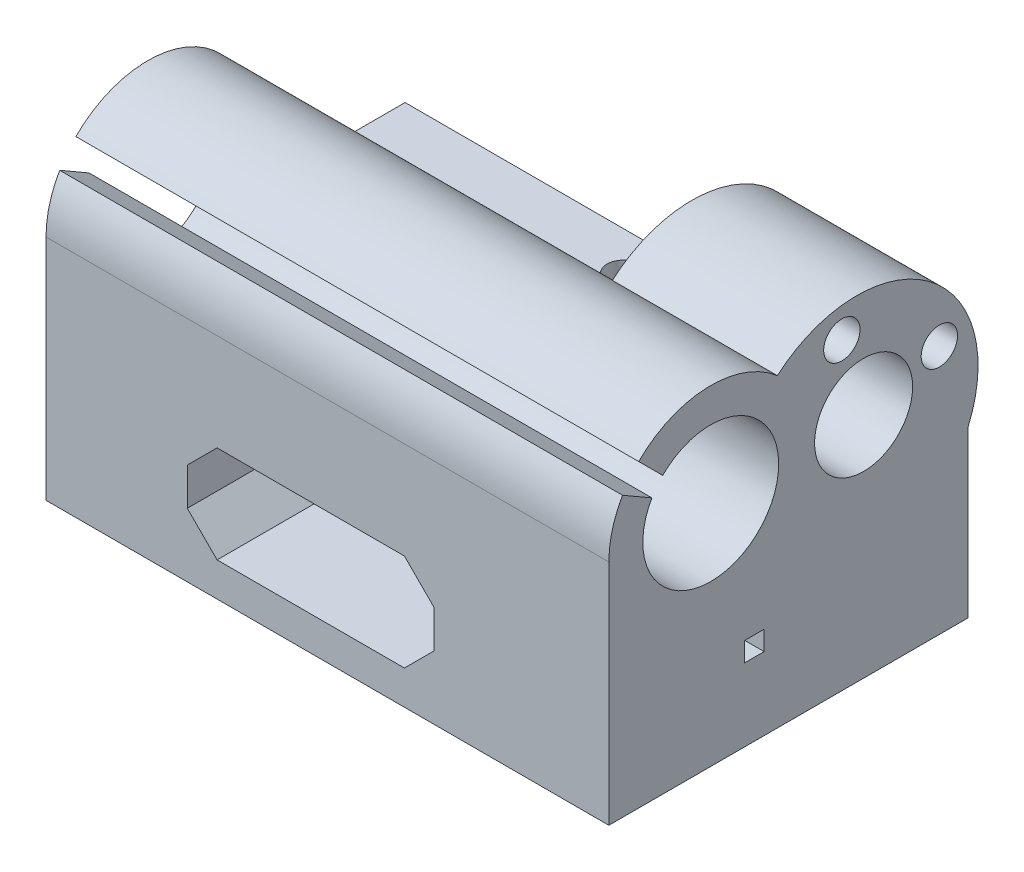
SolidWorks part; units mm, degrees
ref_plane "Front Plane" through (0, 0, 0) normal (0, 0, 1) x (1, 0, 0)
ref_plane "Top Plane" through (0, 0, 0) normal (0, 1, 0) x (1, 0, 0)
ref_plane "Right Plane" through (0, 0, 0) normal (1, 0, 0) x (0, 0, -1)
sketch "Sketch2" plane through (0, 0, 0) normal (0, 1, 0) x (1, 0, 0)
  line L1 (-29, -18.5) -> (29, -18.5)
  line L2 (-29, -18.5) -> (-29, 18.5)
  line L3 (-29, 18.5) -> (29, 18.5)
  line L4 (29, -18.5) -> (29, 18.5)
  line L5 (-29, -18.5) -> (29, 18.5) construction
  line L6 (-29, 18.5) -> (29, -18.5) construction
  point P0 (0, 0)
  dimension "D1" = 58
  dimension "D2" = 37
extrude "Boss-Extrude1" add sketch "Sketch2" along normal blind 17
sketch "Sketch3" plane through (29, 0, 0) normal (1, 0, 0) x (0, 0, -1)
  line L0 (-18.5, 0) -> (18.5, 0) construction
  line L1 (-18.5, 23.5) -> (-18.5, 17)
  line L2 (-18.5, 17) -> (-18.5, 0) construction
  line L5 (2.5, 23.5) -> (2.5, 17)
  line L6 (-18.5, 17) -> (18.5, 17) construction
  line L7 (-18.5, 17) -> (2.5, 17)
  arc A0 (2.5, 23.5) -> (-18.5, 23.5) centre (-8, 23.5) ccw
  dimension "D2" = 21
  dimension "D4" = 23.5
  dimension "D5" = 10.5
extrude "Boss-Extrude2" add sketch "Sketch3" against normal up to surface (58 mm away) up to face at (-29, 8.5, 0)
sketch "Sketch4" plane through (29, 0, 0) normal (1, 0, 0) x (0, 0, -1)
  line L1 (-18.5, 0) -> (18.5, 0) construction
  circle A0 centre (7.0436, 22) radius 12.5
  dimension "D1" = 25
  dimension "D2" = 22
extrude "Boss-Extrude3" add sketch "Sketch4" against normal blind 17
sketch "Sketch5" plane through (0, 0, -18.5) normal (0, 0, -1) x (-1, 0, 0)
  line L0 (-11, 6.57) -> (-11, 10.427)
  line L1 (-11, 10.427) -> (-7.93, 13.497)
  line L2 (-7.93, 13.497) -> (11.37, 13.497)
  line L3 (11.37, 13.497) -> (14.44, 10.427)
  line L4 (14.44, 10.427) -> (14.44, 6.57)
  line L5 (14.44, 6.57) -> (11.37, 3.5)
  line L6 (11.37, 3.5) -> (-7.93, 3.5)
  line L7 (-7.93, 3.5) -> (-11, 6.57)
  line L8 (-29, 0) -> (29, 0) construction
  line L9 (-29, 17) -> (-29, 0) construction
  dimension "D1" = 3.857
  dimension "D2" = 3.857
  dimension "D3" = 135
  dimension "D4" = 135
  dimension "D5" = 3.07
  dimension "D6" = 3.07
  dimension "D7" = 3.07
  dimension "D8" = 3.07
  dimension "D9" = 19.3
  dimension "D10" = 3.5
  dimension "D11" = 18
extrude "Cut-Extrude1" cut sketch "Sketch5" against normal through all
sketch "Sketch6" plane through (0, 0, -18.5) normal (0, 0, -1) x (-1, 0, 0)
  line L0 (-29, 0) -> (29, 0) construction
  line L1 (-29, 17) -> (-29, 0) construction
  circle A0 centre (-23, 8.5) radius 4.076
  circle A1 centre (22, 8.5) radius 4.076
  dimension "D5" = 8.152
  dimension "D6" = 8.152
  dimension "D1" = 8.5
  dimension "D2" = 8.5
  dimension "D3" = 6
  dimension "D4" = 51
extrude "Cut-Extrude2" cut sketch "Sketch6" against normal blind 23
sketch "Sketch7" plane through (29, 0, 0) normal (1, 0, 0) x (0, 0, -1)
  line L0 (-18.5, 23.5) -> (-18.5, 0) construction
  line L1 (-18.5, 0) -> (18.5, 0) construction
  circle A0 centre (-8, 23.5) radius 7
  circle A1 centre (7.7501, 23.5) radius 5.05
  dimension "D1" = 10.1
  dimension "D2" = 14
  dimension "D3" = 26.2501
  dimension "D4" = 23.5
extrude "Cut-Extrude3" cut sketch "Sketch7" against normal through all
sketch "Sketch8" plane through (29, 0, 0) normal (1, 0, 0) x (0, 0, -1)
  line L0 (7.7501, 23.5) -> (5.5097, 31.31) construction
  line L3 (7.7501, 23.5) -> (15.5601, 25.7405) construction
  line L4 (5.5097, 31.31) -> (6.0267, 29.5077) construction
  line L7 (15.5601, 25.7405) -> (13.7578, 25.2235) construction
  circle A1 centre (5.5097, 31.31) radius 1.875
  circle A2 centre (15.5601, 25.7405) radius 1.875
  dimension "D1" = 3.75
  dimension "D2" = 6.25
  dimension "D3" = 3.75
  dimension "D7" = 6.25
extrude "Cut-Extrude4" cut sketch "Sketch8" against normal through all
sketch "Sketch9" plane through (12, 0, 0) normal (-1, 0, 0) x (0, 0, 1)
  circle A0 centre (-5.5097, 31.31) radius 2.75
  circle A1 centre (-15.5601, 25.7405) radius 2.75
  dimension "D1" = 5.5
  dimension "D2" = 5.5
sketch "Sketch10" plane through (29, 0, 0) normal (1, 0, 0) x (0, 0, -1)
  line L0 (-8, 23.5) -> (-15.4246, 30.9246) construction
  line L1 (-8, 23.5) -> (-29.5432, 23.5) construction
  line L2 (-8, 23.5) -> (-17.0933, 28.75) construction
  line L3 (-12.9497, 28.4497) -> (-15.4246, 30.9246)
  line L4 (-17.0933, 28.75) -> (-14.0622, 27)
  arc A0 (-1.1397, 31.449) -> (-18.5, 23.5) centre (-8, 23.5) ccw construction
  arc A1 (-12.9497, 28.4497) -> (-14.0622, 27) centre (-8, 23.5) ccw
  arc A2 (-18.5, 23.5) -> (-17.0933, 28.75) centre (-8, 23.5) ccw
  circle A3 centre (-8, 23.5) radius 7 construction
  circle M9 centre (-8, 23.5) radius 7
  arc M13 (-1.1397, 31.449) -> (-18.5, 23.5) centre (-8, 23.5) ccw
  dimension "D1" = 15
  dimension "D2" = 30
extrude "Cut-Extrude5" cut sketch "Sketch10" against normal through all contours L4 L3 M13 M9 region at (29, 28.8823, 15.0143)
sketch "Sketch12" plane through (-29, 0, 0) normal (-1, 0, 0) x (0, 0, 1)
  line L0 (-18.5, 17) -> (-18.5, 0) construction
  line L1 (4.5, 7.5) -> (2.5, 7.5)
  line L2 (4.5, 7.5) -> (4.5, 9.5)
  line L3 (4.5, 9.5) -> (2.5, 9.5)
  line L4 (2.5, 7.5) -> (2.5, 9.5)
  line L5 (-18.5, 0) -> (18.5, 0) construction
  dimension "D1" = 23
  dimension "D2" = 2
  dimension "D3" = 2
  dimension "D4" = 7.5
extrude "Cut-Extrude6" cut sketch "Sketch12" against normal blind 8
mirror "Mirror1" about plane through (0, 0, 0) normal (1, 0, 0) of "Cut-Extrude6"
sketch "Sketch13" plane through (0, 17, 0) normal (0, 1, 0) x (1, 0, 0)
  line L0 (-29, 18.5) -> (-29, 2.5) construction
  line L1 (12, 18.5) -> (-29, 18.5) construction
  circle A0 centre (-2.525, 14.5) radius 1.6587
  dimension "D2" = 3.3175
  dimension "D1" = 26.475
  dimension "D3" = 4
extrude "Cut-Extrude7" cut sketch "Sketch13" against normal through all
